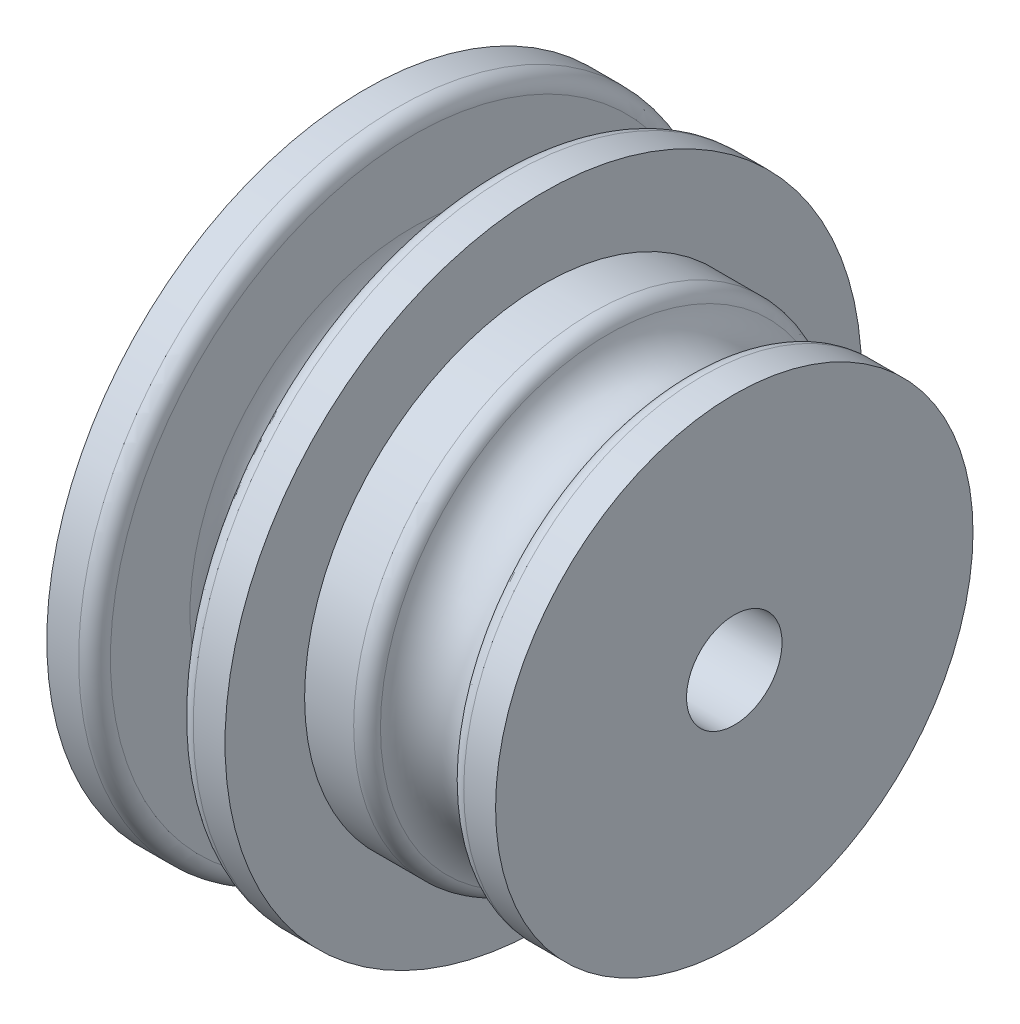
SolidWorks part; units mm, degrees
ref_plane "Front Plane" through (0, 0, 0) normal (1, 0, 0) x (0, 1, 0)
ref_plane "Top Plane" through (0, 0, 0) normal (0, 0, 1) x (0, 1, 0)
ref_plane "Right Plane" through (0, 0, 0) normal (0, 1, 0) x (-1, 0, 0)
sketch "Sketch1" plane through (0, 0, 0) normal (0, 1, 0) x (-1, 0, 0)
  line L0 (-11.6, 0) -> (0, 0)
  line L1 (-11.6, 0) -> (-11.6, 7.5)
  line L2 (-11.6, 7.5) -> (-10.6, 7.5)
  line L3 (-7.1417, 7.5) -> (-5.6, 7.5)
  line L4 (-5.6, 7.5) -> (-5.6, 10)
  line L5 (-5.6, 10) -> (-4.6, 10)
  line L6 (-4.1, 9.5) -> (-4.1, 7)
  line L7 (-1.5, 7) -> (-1.5, 9.5)
  line L8 (-1, 10) -> (0, 10)
  line L9 (0, 10) -> (0, 0)
  line L11 (-5.6, 7.5) -> (-5.6, 0)
  arc A0 (-10.1197, 7.1389) -> (-7.622, 7.1389) centre (-8.8708, 7.5) ccw
  arc A1 (-4.1, 7) -> (-1.5, 7) centre (-2.8, 7) ccw
  arc A2 (-1.5, 9.5) -> (-1, 10) centre (-1, 9.5) cw
  arc A3 (-4.6, 10) -> (-4.1, 9.5) centre (-4.6, 9.5) cw
  arc A4 (-10.6, 7.5) -> (-10.1197, 7.1389) centre (-10.6, 7) cw
  arc A5 (-7.622, 7.1389) -> (-7.1417, 7.5) centre (-7.1417, 7) cw
  point P3 (0, 0)
  dimension "D2" = 1.3
  dimension "D6" = 0.5
  dimension "D1" = 6
  dimension "D3" = 3
  dimension "D5" = 10
  dimension "D7" = 1
  dimension "D4" = 7.5
  dimension "D8" = 1
  dimension "D9" = 1
revolve "Revolve1" add sketch "Sketch1" angle 360 about L0 region at (2.8, 0, 4.303)
revolve "Revolve2" add sketch "Sketch1<3>" angle 360 about L0 region at (8.5826, 0, 3.5434)
sketch "Sketch1<3>" plane through (0, 0, 0) normal (0, 1, 0) x (-1, 0, 0) same geometry as "Sketch1"
sketch "Sketch2" plane through (0, 0, 0) normal (1, 0, 0) x (0, 1, 0)
  circle A0 centre (0, 0) radius 1.5
  dimension "D1" = 3
extrude "Cut-Extrude1" cut sketch "Sketch2" along normal through all
equation "\"A\"= \"D5@Sketch1\""
equation "\"B\"= 3 / 10"
